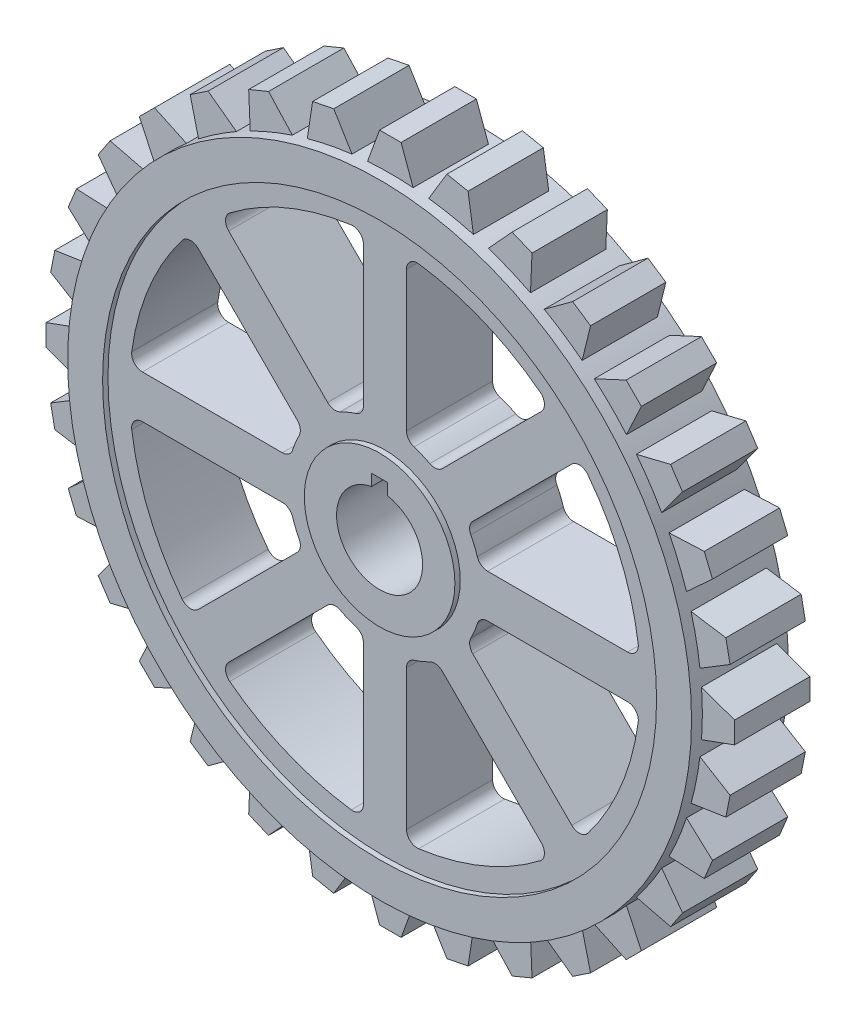
SolidWorks part; units mm, degrees
material "Cast Carbon Steel"
ref_plane "Front Plane" through (0, 0, 0) normal (0, 0, 1) x (1, 0, 0)
ref_plane "Top Plane" through (0, 0, 0) normal (0, 1, 0) x (1, 0, 0)
ref_plane "Right Plane" through (0, 0, 0) normal (1, 0, 0) x (0, 0, -1)
sketch "Sketch1" plane through (0, 0, 0) normal (0, 0, 1) x (1, 0, 0)
  line L1 (1.5, 7.8581) -> (1.5, 10)
  line L2 (1.5, 10) -> (-1.5, 10)
  line L3 (-1.5, 10) -> (-1.5, 7.8581)
  line L4 (0, 10) -> (0, 0) construction
  line L5 (-4, 47.3313) -> (-4, 17.5499)
  line L6 (4, 47.3313) -> (4, 17.5499)
  line L7 (0, 10) -> (0, 47.3313) construction
  line L8 (-4, 47.3313) -> (4, 47.3313) construction
  line L9 (-47.5, 0) -> (-47.3313, 0) construction
  line L10 (0, 56.6578) -> (0, -18) construction
  line L11 (30.6398, 36.2967) -> (9.5812, 15.2381)
  line L12 (36.2967, 30.6398) -> (15.2381, 9.5812)
  line L13 (47.3313, 4) -> (47.3313, -4) construction
  line L14 (0, 0) -> (18, 0) construction
  line L15 (47.3313, 0) -> (47.5, 0) construction
  line L16 (7.0711, 7.0711) -> (33.4683, 33.4683) construction
  line L17 (4, -47.3313) -> (-4, -47.3313) construction
  line L18 (0, 0) -> (0, -18) construction
  line L19 (0, -47.3313) -> (0, -47.5) construction
  line L20 (30.6398, 36.2967) -> (36.2967, 30.6398) construction
  line L21 (-47.3313, -4) -> (-47.3313, 4) construction
  line L22 (0, 0) -> (-18, 0) construction
  line L23 (-18, 0) -> (18, 0) construction
  line L24 (-47.3313, 4) -> (-17.5499, 4) [skipped]
  line L25 (-47.3313, -4) -> (-17.5499, -4) [skipped]
  line L26 (-4, -47.3313) -> (-4, -17.5499) [skipped]
  line L27 (4, -47.3313) -> (4, -17.5499) [skipped]
  line L28 (47.3313, -4) -> (17.5499, -4) [skipped]
  line L29 (47.3313, 4) -> (17.5499, 4) [skipped]
  line L30 (47.3313, 4) -> (17.5499, 4)
  line L31 (47.3313, -4) -> (17.5499, -4)
  line L32 (10, 0) -> (47.3313, 0) construction
  line L33 (47.3313, 4) -> (47.3313, -4) construction
  line L34 (36.2967, -30.6398) -> (15.2381, -9.5812)
  line L35 (30.6398, -36.2967) -> (9.5812, -15.2381)
  line L36 (7.0711, -7.0711) -> (33.4683, -33.4683) construction
  line L37 (36.2967, -30.6398) -> (30.6398, -36.2967) construction
  line L38 (4, -47.3313) -> (4, -17.5499)
  line L39 (-4, -47.3313) -> (-4, -17.5499)
  line L40 (0, -10) -> (0, -47.3313) construction
  line L41 (4, -47.3313) -> (-4, -47.3313) construction
  line L42 (-30.6398, -36.2967) -> (-9.5812, -15.2381)
  line L43 (-36.2967, -30.6398) -> (-15.2381, -9.5812)
  line L44 (-7.0711, -7.0711) -> (-33.4683, -33.4683) construction
  line L45 (-30.6398, -36.2967) -> (-36.2967, -30.6398) construction
  line L46 (-47.3313, -4) -> (-17.5499, -4)
  line L47 (-47.3313, 4) -> (-17.5499, 4)
  line L48 (-10, 0) -> (-47.3313, 0) construction
  line L49 (-47.3313, -4) -> (-47.3313, 4) construction
  line L50 (-36.2967, 30.6398) -> (-15.2381, 9.5812)
  line L51 (-30.6398, 36.2967) -> (-9.5812, 15.2381)
  line L52 (-7.0711, 7.0711) -> (-33.4683, 33.4683) construction
  line L53 (-36.2967, 30.6398) -> (-30.6398, 36.2967) construction
  arc A0 (-1.5, 7.8581) -> (1.5, 7.8581) centre (0, 0) ccw
  circle A1 centre (0, 0) radius 14
  circle A2 centre (0, 0) radius 18
  circle A3 centre (0, 0) radius 58
  circle A4 centre (0, 0) radius 51.5
  circle A5 centre (0, 0) radius 47.5
  circle A6 centre (0, 0) radius 64
  point P20 (0, 47.3313)
  point P25 (0, 0)
  point P46 (0, 0)
  point P93 (0, 0)
  dimension "D1" = 8
  dimension "D4" = 28
  dimension "D12" = 128
  dimension "D2" = 3
  dimension "D3" = 10
  dimension "D7" = 6.5
  dimension "D8" = 4
  dimension "D9" = 8
  dimension "D6" = 6
  dimension "D5" = 4
  dimension "D10" = 4
  dimension "D11" = 8
extrude "Boss-Extrude2" add sketch "Sketch1" along normal mid plane 18 contours A3 A4 region at (-56.3595, 0, 0)
extrude "Boss-Extrude3" add sketch "Sketch1<4>" along normal mid plane 16 contours A4 A5 | L51 A5 L50 A2 | L47 A5 L46 A2 | L43 A5 L42 A2 | L39 A5 L38 A2 | L35 A5 L34 A2 | L31 A5 L30 A2 | L6 A5 L5 A2 | L12 A5 L11 A2 | A2 A1 region at (0, 32.647, 0) region at (0, 17.4909, 0) region at (-23.0849, 23.0849, 0) region at (23.0849, 23.0849, 0) region at (-32.647, 0, 0) region at (32.647, 0, 0) region at (-23.0849, -23.0849, 0) region at (23.0849, -23.0849, 0) region at (0, -32.647, 0) region at (-50.0434, 0, 0)
sketch "Sketch1<4>" plane through (0, 0, 0) normal (0, 0, 1) x (1, 0, 0) same geometry as "Sketch1"
extrude "Boss-Extrude4" add sketch "Sketch1<5>" along normal mid plane 18 contours A1 A0 L3 L2 L1 region at (-13.604, 0, 0)
sketch "Sketch1<5>" plane through (0, 0, 0) normal (0, 0, 1) x (1, 0, 0) same geometry as "Sketch1"
sketch "Sketch4" plane through (0, 0, 0) normal (0, 0, 1) x (1, 0, 0)
  line L0 (-4.2403, 57.8448) -> (-2, 64)
  line L1 (-2, 64) -> (2, 64)
  line L2 (2, 64) -> (4.2403, 57.8448)
  line L3 (0, -6.2531) -> (0, 81.0007) construction
  line L4 (10.5242, 63.1604) -> (14.4474, 62.3801)
  line L5 (7.1261, 57.5606) -> (10.5242, 63.1604)
  line L6 (14.4474, 62.3801) -> (15.4438, 55.9061)
  line L7 (-1.2199, -6.133) -> (15.8024, 79.4443) construction
  line L8 (22.644, 59.8937) -> (26.3395, 58.3629)
  line L9 (18.2187, 55.0643) -> (22.644, 59.8937)
  line L10 (26.3395, 58.3629) -> (26.0538, 51.8189)
  line L11 (-2.393, -5.7771) -> (30.9976, 74.8349) construction
  line L12 (33.8936, 54.3252) -> (37.2194, 52.1029)
  line L13 (28.6112, 50.452) -> (33.8936, 54.3252)
  line L14 (37.2194, 52.1029) -> (35.6625, 45.7404)
  line L15 (-3.474, -5.1993) -> (45.0016, 67.3496) construction
  line L16 (43.8406, 46.669) -> (46.669, 43.8406)
  line L17 (37.9041, 43.9008) -> (43.8406, 46.669)
  line L18 (46.669, 43.8406) -> (43.9008, 37.9041)
  line L19 (-4.4216, -4.4216) -> (57.2761, 57.2761) construction
  line L20 (52.1029, 37.2194) -> (54.3252, 33.8936)
  line L21 (45.7404, 35.6625) -> (52.1029, 37.2194)
  line L22 (54.3252, 33.8936) -> (50.452, 28.6112)
  line L23 (-5.1993, -3.474) -> (67.3496, 45.0016) construction
  line L24 (58.3629, 26.3395) -> (59.8937, 22.644)
  line L25 (51.8189, 26.0538) -> (58.3629, 26.3395)
  line L26 (59.8937, 22.644) -> (55.0643, 18.2187)
  line L27 (-5.7771, -2.393) -> (74.8349, 30.9976) construction
  line L28 (62.3801, 14.4474) -> (63.1604, 10.5242)
  line L29 (55.9061, 15.4438) -> (62.3801, 14.4474)
  line L30 (63.1604, 10.5242) -> (57.5606, 7.1261)
  line L31 (-6.133, -1.2199) -> (79.4443, 15.8024) construction
  line L32 (64, 2) -> (64, -2)
  line L33 (57.8448, 4.2403) -> (64, 2)
  line L34 (64, -2) -> (57.8448, -4.2403)
  line L35 (-6.2531, 0) -> (81.0007, 0) construction
  line L36 (63.1604, -10.5242) -> (62.3801, -14.4474)
  line L37 (57.5606, -7.1261) -> (63.1604, -10.5242)
  line L38 (62.3801, -14.4474) -> (55.9061, -15.4438)
  line L39 (-6.133, 1.2199) -> (79.4443, -15.8024) construction
  line L40 (59.8937, -22.644) -> (58.3629, -26.3395)
  line L41 (55.0643, -18.2187) -> (59.8937, -22.644)
  line L42 (58.3629, -26.3395) -> (51.8189, -26.0538)
  line L43 (-5.7771, 2.393) -> (74.8349, -30.9976) construction
  line L44 (54.3252, -33.8936) -> (52.1029, -37.2194)
  line L45 (50.452, -28.6112) -> (54.3252, -33.8936)
  line L46 (52.1029, -37.2194) -> (45.7404, -35.6625)
  line L47 (-5.1993, 3.474) -> (67.3496, -45.0016) construction
  line L48 (46.669, -43.8406) -> (43.8406, -46.669)
  line L49 (43.9008, -37.9041) -> (46.669, -43.8406)
  line L50 (43.8406, -46.669) -> (37.9041, -43.9008)
  line L51 (-4.4216, 4.4216) -> (57.2761, -57.2761) construction
  line L52 (37.2194, -52.1029) -> (33.8936, -54.3252)
  line L53 (35.6625, -45.7404) -> (37.2194, -52.1029)
  line L54 (33.8936, -54.3252) -> (28.6112, -50.452)
  line L55 (-3.474, 5.1993) -> (45.0016, -67.3496) construction
  line L56 (26.3395, -58.3629) -> (22.644, -59.8937)
  line L57 (26.0538, -51.8189) -> (26.3395, -58.3629)
  line L58 (22.644, -59.8937) -> (18.2187, -55.0643)
  line L59 (-2.393, 5.7771) -> (30.9976, -74.8349) construction
  line L60 (14.4474, -62.3801) -> (10.5242, -63.1604)
  line L61 (15.4438, -55.9061) -> (14.4474, -62.3801)
  line L62 (10.5242, -63.1604) -> (7.1261, -57.5606)
  line L63 (-1.2199, 6.133) -> (15.8024, -79.4443) construction
  line L64 (2, -64) -> (-2, -64)
  line L65 (4.2403, -57.8448) -> (2, -64)
  line L66 (-2, -64) -> (-4.2403, -57.8448)
  line L67 (0, 6.2531) -> (0, -81.0007) construction
  line L68 (-10.5242, -63.1604) -> (-14.4474, -62.3801)
  line L69 (-7.1261, -57.5606) -> (-10.5242, -63.1604)
  line L70 (-14.4474, -62.3801) -> (-15.4438, -55.9061)
  line L71 (1.2199, 6.133) -> (-15.8024, -79.4443) construction
  line L72 (-22.644, -59.8937) -> (-26.3395, -58.3629)
  line L73 (-18.2187, -55.0643) -> (-22.644, -59.8937)
  line L74 (-26.3395, -58.3629) -> (-26.0538, -51.8189)
  line L75 (2.393, 5.7771) -> (-30.9976, -74.8349) construction
  line L76 (-33.8936, -54.3252) -> (-37.2194, -52.1029)
  line L77 (-28.6112, -50.452) -> (-33.8936, -54.3252)
  line L78 (-37.2194, -52.1029) -> (-35.6625, -45.7404)
  line L79 (3.474, 5.1993) -> (-45.0016, -67.3496) construction
  line L80 (-43.8406, -46.669) -> (-46.669, -43.8406)
  line L81 (-37.9041, -43.9008) -> (-43.8406, -46.669)
  line L82 (-46.669, -43.8406) -> (-43.9008, -37.9041)
  line L83 (4.4216, 4.4216) -> (-57.2761, -57.2761) construction
  line L84 (-52.1029, -37.2194) -> (-54.3252, -33.8936)
  line L85 (-45.7404, -35.6625) -> (-52.1029, -37.2194)
  line L86 (-54.3252, -33.8936) -> (-50.452, -28.6112)
  line L87 (5.1993, 3.474) -> (-67.3496, -45.0016) construction
  line L88 (-58.3629, -26.3395) -> (-59.8937, -22.644)
  line L89 (-51.8189, -26.0538) -> (-58.3629, -26.3395)
  line L90 (-59.8937, -22.644) -> (-55.0643, -18.2187)
  line L91 (5.7771, 2.393) -> (-74.8349, -30.9976) construction
  line L92 (-62.3801, -14.4474) -> (-63.1604, -10.5242)
  line L93 (-55.9061, -15.4438) -> (-62.3801, -14.4474)
  line L94 (-63.1604, -10.5242) -> (-57.5606, -7.1261)
  line L95 (6.133, 1.2199) -> (-79.4443, -15.8024) construction
  line L96 (-64, -2) -> (-64, 2)
  line L97 (-57.8448, -4.2403) -> (-64, -2)
  line L98 (-64, 2) -> (-57.8448, 4.2403)
  line L99 (6.2531, 0) -> (-81.0007, 0) construction
  line L100 (-63.1604, 10.5242) -> (-62.3801, 14.4474)
  line L101 (-57.5606, 7.1261) -> (-63.1604, 10.5242)
  line L102 (-62.3801, 14.4474) -> (-55.9061, 15.4438)
  line L103 (6.133, -1.2199) -> (-79.4443, 15.8024) construction
  line L104 (-59.8937, 22.644) -> (-58.3629, 26.3395)
  line L105 (-55.0643, 18.2187) -> (-59.8937, 22.644)
  line L106 (-58.3629, 26.3395) -> (-51.8189, 26.0538)
  line L107 (5.7771, -2.393) -> (-74.8349, 30.9976) construction
  line L108 (-54.3252, 33.8936) -> (-52.1029, 37.2194)
  line L109 (-50.452, 28.6112) -> (-54.3252, 33.8936)
  line L110 (-52.1029, 37.2194) -> (-45.7404, 35.6625)
  line L111 (5.1993, -3.474) -> (-67.3496, 45.0016) construction
  line L112 (-46.669, 43.8406) -> (-43.8406, 46.669)
  line L113 (-43.9008, 37.9041) -> (-46.669, 43.8406)
  line L114 (-43.8406, 46.669) -> (-37.9041, 43.9008)
  line L115 (4.4216, -4.4216) -> (-57.2761, 57.2761) construction
  line L116 (-37.2194, 52.1029) -> (-33.8936, 54.3252)
  line L117 (-35.6625, 45.7404) -> (-37.2194, 52.1029)
  line L118 (-33.8936, 54.3252) -> (-28.6112, 50.452)
  line L119 (3.474, -5.1993) -> (-45.0016, 67.3496) construction
  line L120 (-26.3395, 58.3629) -> (-22.644, 59.8937)
  line L121 (-26.0538, 51.8189) -> (-26.3395, 58.3629)
  line L122 (-22.644, 59.8937) -> (-18.2187, 55.0643)
  line L123 (2.393, -5.7771) -> (-30.9976, 74.8349) construction
  line L124 (-14.4474, 62.3801) -> (-10.5242, 63.1604)
  line L125 (-15.4438, 55.9061) -> (-14.4474, 62.3801)
  line L126 (-10.5242, 63.1604) -> (-7.1261, 57.5606)
  line L127 (1.2199, -6.133) -> (-15.8024, 79.4443) construction
  circle A0 centre (0, 0) radius 58
  circle A1 centre (0, 0) radius 58 construction
  circle A2 centre (0, 0) radius 58
  circle A3 centre (0, 0) radius 58
  circle A4 centre (0, 0) radius 58
  circle A5 centre (0, 0) radius 58
  circle A6 centre (0, 0) radius 58
  circle A7 centre (0, 0) radius 58
  circle A8 centre (0, 0) radius 58
  circle A9 centre (0, 0) radius 58
  circle A10 centre (0, 0) radius 58
  circle A11 centre (0, 0) radius 58
  circle A12 centre (0, 0) radius 58
  circle A13 centre (0, 0) radius 58
  circle A14 centre (0, 0) radius 58
  circle A15 centre (0, 0) radius 58
  circle A16 centre (0, 0) radius 58
  circle A17 centre (0, 0) radius 58
  circle A18 centre (0, 0) radius 58
  circle A19 centre (0, 0) radius 58
  circle A20 centre (0, 0) radius 58
  circle A21 centre (0, 0) radius 58
  circle A22 centre (0, 0) radius 58
  circle A23 centre (0, 0) radius 58
  circle A24 centre (0, 0) radius 58
  circle A25 centre (0, 0) radius 58
  circle A30 centre (0, 0) radius 58
  circle A31 centre (0, 0) radius 58
  circle A32 centre (0, 0) radius 58
  circle A33 centre (0, 0) radius 58
  circle A34 centre (0, 0) radius 58
  circle A35 centre (0, 0) radius 58
  circle A36 centre (0, 0) radius 58
  circle A37 centre (0, 0) radius 58
  point P5 (0, 64)
  point P16 (0, 58)
  point P150 (0, 0)
  dimension "D2" = 4
  dimension "D3" = 40
  dimension "D4" = 6
  dimension "D5" = 32
extrude "Boss-Extrude5" add sketch "Sketch4" along normal mid plane 14 contours A0 L70 L68 L69 | A0 L66 L64 L65 | A0 L74 L72 L73 | A0 L78 L76 L77 | A0 L82 L80 L81 | A0 L86 L84 L85 | A0 L90 L88 L89 | A0 L94 L92 L93 | A0 L2 L1 L0 | A0 L6 L4 L5 | A0 L10 L8 L9 | A0 L14 L12 L13 | A0 L62 L60 L61 | A0 L58 L56 L57 | A0 L54 L52 L53 | A0 L50 L48 L49 | A0 L46 L44 L45 | A0 L42 L40 L41 | A0 L38 L36 L37 | A0 L34 L32 L33 | A0 L30 L28 L29 | A0 L26 L24 L25 | A0 L22 L20 L21 | A0 L18 L16 L17 | A0 L96 | A0 L100 | A0 L104 | A0 L108 | A0 L114 L112 L113 | A0 L118 L116 L117 | A0 L122 L120 L121 | A0 L126 L124 L125 region at (0, 60.616, 0) region at (-11.8256, 59.4513, 0) region at (11.8256, 59.4513, 0) region at (-23.1967, 56.0019, 0) region at (23.1967, 56.0019, 0) region at (-33.6765, 50.4004, 0) region at (33.6765, 50.4004, 0) region at (-42.862, 42.862, 0) region at (42.862, 42.862, 0) region at (-50.4004, 33.6765, 0) region at (50.4004, 33.6765, 0) region at (-56.0019, 23.1967, 0) region at (56.0019, 23.1967, 0) region at (-59.4513, 11.8256, 0) region at (59.4513, 11.8256, 0) region at (-60.616, 0, 0) region at (60.616, 0, 0) region at (-59.4513, -11.8256, 0) region at (59.4513, -11.8256, 0) region at (-56.0019, -23.1967, 0) region at (56.0019, -23.1967, 0) region at (-50.4004, -33.6765, 0) region at (50.4004, -33.6765, 0) region at (-42.862, -42.862, 0) region at (42.862, -42.862, 0) region at (-33.6765, -50.4004, 0) region at (33.6765, -50.4004, 0) region at (-23.1967, -56.0019, 0) region at (23.1967, -56.0019, 0) region at (-11.8256, -59.4513, 0) region at (11.8256, -59.4513, 0) region at (0, -60.616, 0)
fillet "Fillet1" radius 2 32 edges at (-47.3313, -4, 0) (-36.2967, -30.6398, 0) (-15.2381, -9.5812, 0) (-17.5499, -4, 0) (-9.5812, -15.2381, 0) (-4, -17.5499, 0) (-30.6398, -36.2967, 0) (-4, -47.3313, 0) (30.6398, -36.2967, 0) (4, -47.3313, 0) (9.5812, -15.2381, 0) (4, -17.5499, 0) (36.2967, -30.6398, 0) (15.2381, -9.5812, 0) (17.5499, -4, 0) (47.3313, -4, 0) (17.5499, 4, 0) (47.3313, 4, 0) (15.2381, 9.5812, 0) (36.2967, 30.6398, 0) (30.6398, 36.2967, 0) (4, 47.3313, 0) (9.5812, 15.2381, 0) (4, 17.5499, 0) (-4, 17.5499, 0) (-4, 47.3313, 0) (-9.5812, 15.2381, 0) (-30.6398, 36.2967, 0) (-15.2381, 9.5812, 0) (-17.5499, 4, 0) (-36.2967, 30.6398, 0) (-47.3313, 4, 0)
equation "\"A\" = 128"
equation "\"B\" = 32"
equation "\"C\"= 4"
equation "\"D5@Sketch1\"=\"C\""
equation "\"D8@Sketch1\"=\"C\""
equation "\"D9@Sketch1\"=\"C\"*2"
equation "\"D5@Sketch4\"=\"B\""
equation "\"D12@Sketch1\"=\"A\""
